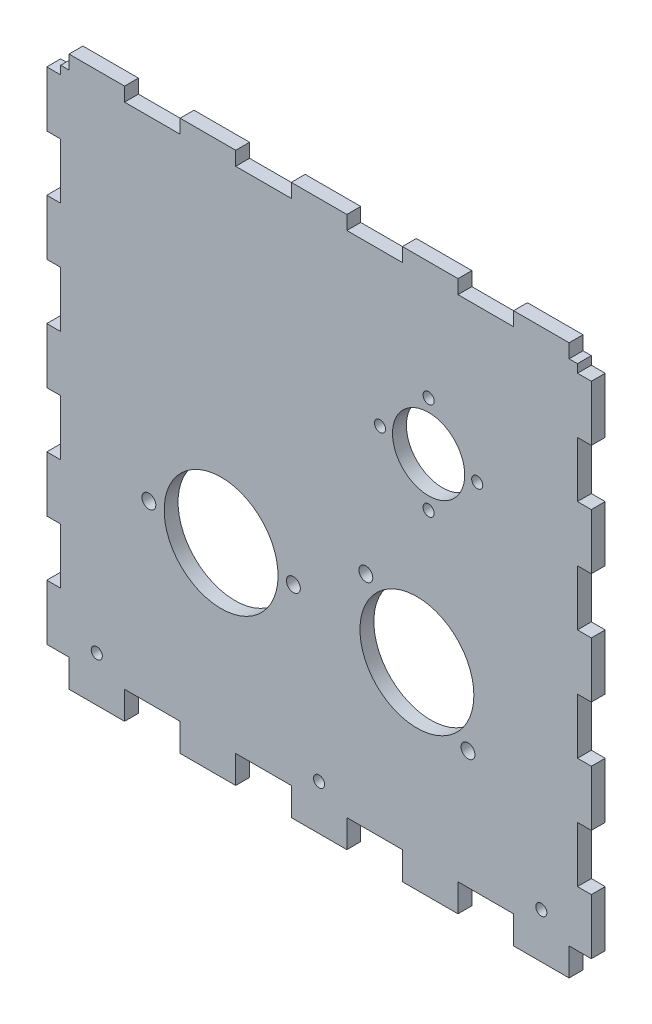
SolidWorks part; units mm, degrees
material "아크릴(내충격성)"
ref_plane "정면" through (0, 0, 0) normal (0, 0, 1) x (1, 0, 0)
ref_plane "윗면" through (0, 0, 0) normal (0, 1, 0) x (1, 0, 0)
ref_plane "우측면" through (0, 0, 0) normal (1, 0, 0) x (0, 0, -1)
sketch "스케치1" plane through (0, 0, 0) normal (0, 0, 1) x (1, 0, 0)
  line L0 (-35.25, 48.411) -> (-35.25, -111.4061) construction
  line L1 (-93, 91.5) -> (93, 91.5)
  line L2 (-93, 91.5) -> (-93, -91.5)
  line L3 (-93, -91.5) -> (93, -91.5)
  line L4 (93, 91.5) -> (93, -91.5)
  line L5 (-93, 91.5) -> (93, -91.5) construction
  line L6 (-93, -91.5) -> (93, 91.5) construction
  line L7 (39.4226, 64.8355) -> (39.4226, -71.9738) construction
  line L8 (0, 68.0997) -> (0, -64.9282) construction
  line L9 (67.9316, -30.5) -> (15.9316, -30.5) construction
  line L10 (11.3218, -6.6001) -> (50.8051, -46.0834) construction
  circle A1 centre (-35.25, -28.5) radius 20.5
  circle A4 centre (-61.25, -28.5) radius 2.5
  circle A5 centre (-9.25, -28.5) radius 2.5
  circle A6 centre (39.4226, 36.5) radius 21 construction
  circle A9 centre (35.2216, -30.5) radius 20.5
  circle A10 centre (16.8368, -12.1152) radius 2.5
  circle A11 centre (53.6064, -48.8848) radius 2.5
  circle A12 centre (39.4226, 36.5) radius 17.5 construction
  circle A13 centre (39.4226, 19) radius 2
  circle A14 centre (39.4226, 36.5) radius 13
  circle A18 centre (21.9226, 36.5) radius 2
  circle A19 centre (39.4226, 54) radius 2
  circle A20 centre (56.9226, 36.5) radius 2
  point P0 (0, 0)
  point P44 (39.4226, 36.5)
  dimension "D3" = 41
  dimension "D8" = 52
  dimension "D9" = 5
  dimension "D10" = 55
  dimension "D11" = 42
  dimension "D12" = 4
  dimension "D14" = 41
  dimension "D15" = 70.5
  dimension "D17" = 5
  dimension "D20" = 26
  dimension "D1" = 183
  dimension "D2" = 186
  dimension "D4" = 3.5
  dimension "D5" = 63
  dimension "D6" = 99
  dimension "D7" = 35.25
  dimension "D13" = 61
  dimension "D16" = 45
  dimension "D18" = 26
  dimension "D19" = 26
  dimension "D21" = 4
extrude "보스-돌출1" add sketch "스케치1" along normal blind 5
sketch "스케치2" plane through (0, 0, 5) normal (0, 0, 1) x (1, 0, 0)
  line L1 (-93, -91.5) -> (-98, -91.5)
  line L2 (-93, -91.5) -> (-93, -71.5)
  line L3 (-93, -71.5) -> (-98, -71.5)
  line L4 (-98, -91.5) -> (-98, -71.5)
  dimension "D1" = 5
  dimension "D2" = 20
extrude "보스-돌출2" add sketch "스케치2" against normal up to surface (5 mm away) up to face at (0, 0, 0)
pattern_linear "선형 패턴1" count 5 spacing 40 along (0, 1, 0) of "보스-돌출2"
mirror "대칭 복사1" about plane through (0, 0, 0) normal (1, 0, 0) of "선형 패턴1"
sketch "스케치3" plane through (0, 0, 5) normal (0, 0, 1) x (1, 0, 0)
  line L0 (93, 91.5) -> (-93, 91.5) construction
  line L1 (10, 91.5) -> (-10, 91.5)
  line L2 (10, 91.5) -> (10, 96.5)
  line L3 (10, 96.5) -> (-10, 96.5)
  line L4 (-10, 91.5) -> (-10, 96.5)
  line L5 (0, 262.1917) -> (0, -69.1917) construction
  point P9 (0, 96.5)
  dimension "D1" = 20
  dimension "D2" = 5
extrude "보스-돌출3" add sketch "스케치3" against normal up to surface (5 mm away) up to face at (0, 7.65, 0)
pattern_linear "선형 패턴2" count 3 spacing 40 along (1, 0, 0) of "보스-돌출3"
pattern_linear "선형 패턴3" count 3 spacing 40 along (-1, 0, 0) of "보스-돌출3"
sketch "스케치4" plane through (0, 0, 5) normal (0, 0, 1) x (1, 0, 0)
  line L0 (-98, -91.5) -> (98, -91.5) construction
  line L1 (-10, -91.5) -> (10, -91.5)
  line L2 (-10, -91.5) -> (-10, -101.5)
  line L3 (-10, -101.5) -> (10, -101.5)
  line L4 (10, -91.5) -> (10, -101.5)
  line L5 (0, -83.6889) -> (0, -110.8852) construction
  dimension "D1" = 20
  dimension "D2" = 10
extrude "보스-돌출4" add sketch "스케치4" against normal up to surface (5 mm away) up to face at (0, 36.4333, 0)
pattern_linear "선형 패턴4" count 3 spacing 40 along (1, 0, 0) of "보스-돌출4"
pattern_linear "선형 패턴5" count 3 spacing 40 along (-1, 0, 0) of "선형 패턴4"
sketch "스케치5" plane through (0, 0, 0) normal (0, 0, -1) x (-1, 0, 0)
  line L0 (0, -66.2628) -> (0, -108.7434) construction
  line L1 (-10, -91.5) -> (-30, -91.5) construction
  circle A0 centre (0, -85.2) radius 2
  dimension "D1" = 4
  dimension "D2" = 6.3
extrude "컷-돌출1" cut sketch "스케치5" against normal up to next
pattern_linear "선형 패턴6" count 2 spacing 80 along (1, 0, 0) of "컷-돌출1"
pattern_linear "선형 패턴7" count 2 spacing 80 along (-1, 0, 0) of "컷-돌출1"
